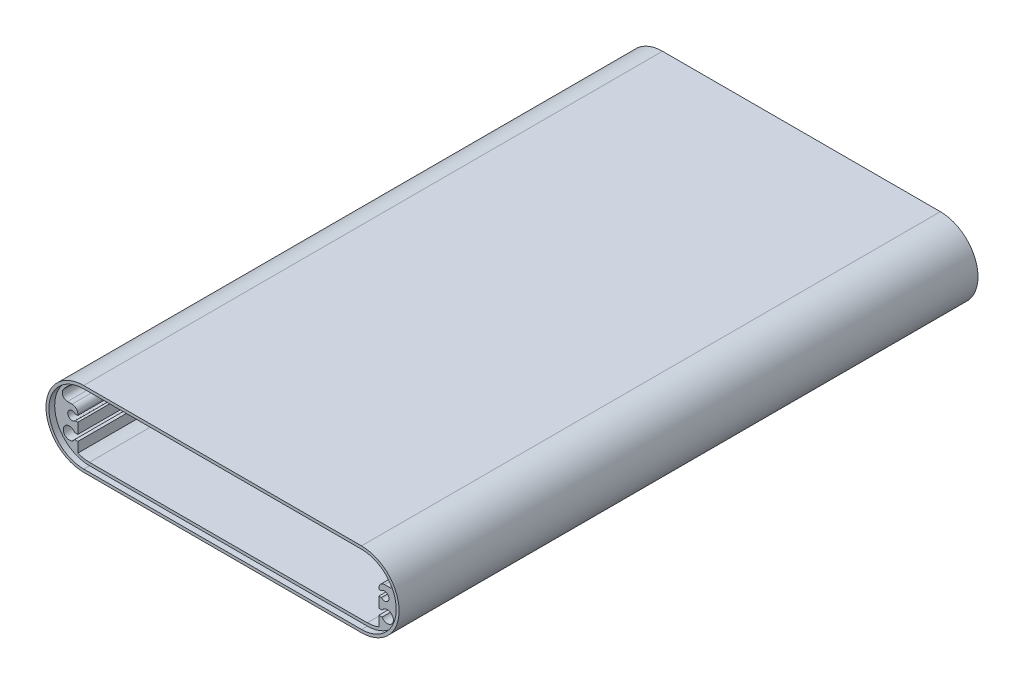
SolidWorks part; units mm, degrees
ref_plane "Front Plane" through (0, 0, 0) normal (0, 0, 1) x (1, 0, 0)
ref_plane "Top Plane" through (0, 0, 0) normal (0, 1, 0) x (1, 0, 0)
ref_plane "Right Plane" through (0, 0, 0) normal (1, 0, 0) x (0, 0, -1)
sketch "Sketch1" plane through (0, 0, 0) normal (0, 0, 1) x (1, 0, 0)
  line L0 (0, 0) -> (0, 16.0369) construction
  line L1 (30.5, 0) -> (-30.5, 0) construction
  line L2 (24, 6.5) -> (-24, 6.5)
  line L3 (24, -6.5) -> (-24, -6.5)
  line L4 (0, 0) -> (0, -11.8688) construction
  line L5 (24, 5.5) -> (-24, 5.5)
  line L6 (-24, -5.5) -> (24, -5.5)
  line L7 (27, 1.7) -> (27.7947, 1.7)
  line L8 (26, 0.5) -> (26, 0.7)
  line L9 (-26, -0.5) -> (-26.441, -0.5)
  line L10 (-26.441, 0.5) -> (-26, 0.5)
  line L11 (-26, -5.1235) -> (-26, -3.375)
  line L12 (-26, -3.375) -> (-26.5557, -3.375)
  line L13 (-26.5557, -2.325) -> (-26, -2.325)
  line L14 (-26, -2.325) -> (-26, -0.5)
  line L15 (-26, 0.5) -> (-26, 0.7)
  line L16 (-27, 1.7) -> (-27.7947, 1.7)
  line L17 (26, -2.325) -> (26, -0.5)
  line L18 (26.5557, -2.325) -> (26, -2.325)
  line L19 (26, -3.375) -> (26.5557, -3.375)
  line L20 (26, -5.1235) -> (26, -3.375)
  line L21 (26.441, 0.5) -> (26, 0.5)
  line L22 (26, -0.5) -> (26.441, -0.5)
  arc A0 (-24, 6.5) -> (-24, -6.5) centre (-24, 0) ccw
  arc A1 (-24, 5.5) -> (-28.5372, 3.1087) centre (-24, 0) ccw
  arc A2 (-26.5557, -2.325) -> (-26.5557, -3.375) centre (-27.465, -2.85) ccw
  arc A3 (-26.441, 0.5) -> (-26.441, -0.5) centre (-27, 0) ccw
  arc A4 (-27, 1.7) -> (-26, 0.7) centre (-27, 0.7) cw
  arc A5 (-26, -5.1235) -> (-24, -5.5) centre (-24, 0) ccw
  arc A6 (-27.7947, 1.7) -> (-28.5372, 3.1087) centre (-27.7947, 2.6) cw
  arc A7 (27.7947, 1.7) -> (28.5372, 3.1087) centre (27.7947, 2.6) ccw
  arc A8 (26, -5.1235) -> (24, -5.5) centre (24, 0) cw
  arc A9 (27, 1.7) -> (26, 0.7) centre (27, 0.7) ccw
  arc A10 (26.441, 0.5) -> (26.441, -0.5) centre (27, 0) cw
  arc A11 (26.5557, -2.325) -> (26.5557, -3.375) centre (27.465, -2.85) cw
  arc A12 (24, 5.5) -> (28.5372, 3.1087) centre (24, 0) cw
  arc A13 (24, 6.5) -> (24, -6.5) centre (24, 0) cw
  point P3 (-36.757, 33.8299)
  point P6 (0, 6.5)
  point P10 (0, -6.5)
  point P15 (0, 5.5)
  point P23 (-30.5, 0)
  point P56 (0, -5.5)
  dimension "D2" = 6.5
  dimension "D4" = 5.5
  dimension "D5" = 2.1
  dimension "D6" = 1.5
  dimension "D7" = 27
  dimension "D8" = 30.5
  dimension "D16" = 1
  dimension "D17" = 0.9
  dimension "D19" = 1.7
  dimension "D1" = 13
  dimension "D3" = 1
  dimension "D9" = 27.465
  dimension "D10" = 1
  dimension "D11" = 0.5
  dimension "D12" = 26
  dimension "D13" = 1.05
  dimension "D14" = 0.525
  dimension "D15" = 3.65
  dimension "D20" = 1
extrude "Boss-Extrude1" add sketch "Sketch1" along normal blind 50 and the other way blind 50
sketch "Sketch2" plane through (0, 0, 50) normal (0, 0, 1) x (1, 0, 0)
  line L0 (24, 6.5) -> (-24, 6.5) construction
  line L1 (-24, -6.5) -> (24, -6.5) construction
  line L2 (24, 6.5) -> (-24, 6.5) construction
  line L3 (-24, -6.5) -> (24, -6.5) construction
  line L4 (24, 6) -> (-24, 6)
  line L5 (-24, -6) -> (24, -6)
  arc A0 (-24, 6.5) -> (-24, -6.5) centre (-24, 0) ccw construction
  arc A1 (24, -6.5) -> (24, 6.5) centre (24, 0) ccw construction
  arc A2 (-24, 6.5) -> (-24, -6.5) centre (-24, 0) ccw construction
  arc A3 (24, -6.5) -> (24, 6.5) centre (24, 0) ccw construction
  arc A4 (-24, 6) -> (-24, -6) centre (-24, 0) ccw
  arc A5 (24, -6) -> (24, 6) centre (24, 0) ccw
  dimension "D1" = 0.5
extrude "Cut-Extrude1" cut sketch "Sketch2" against normal blind 1
mirror "Mirror1" about plane through (0, 0, 0) normal (0, 0, 1) of "Cut-Extrude1"
